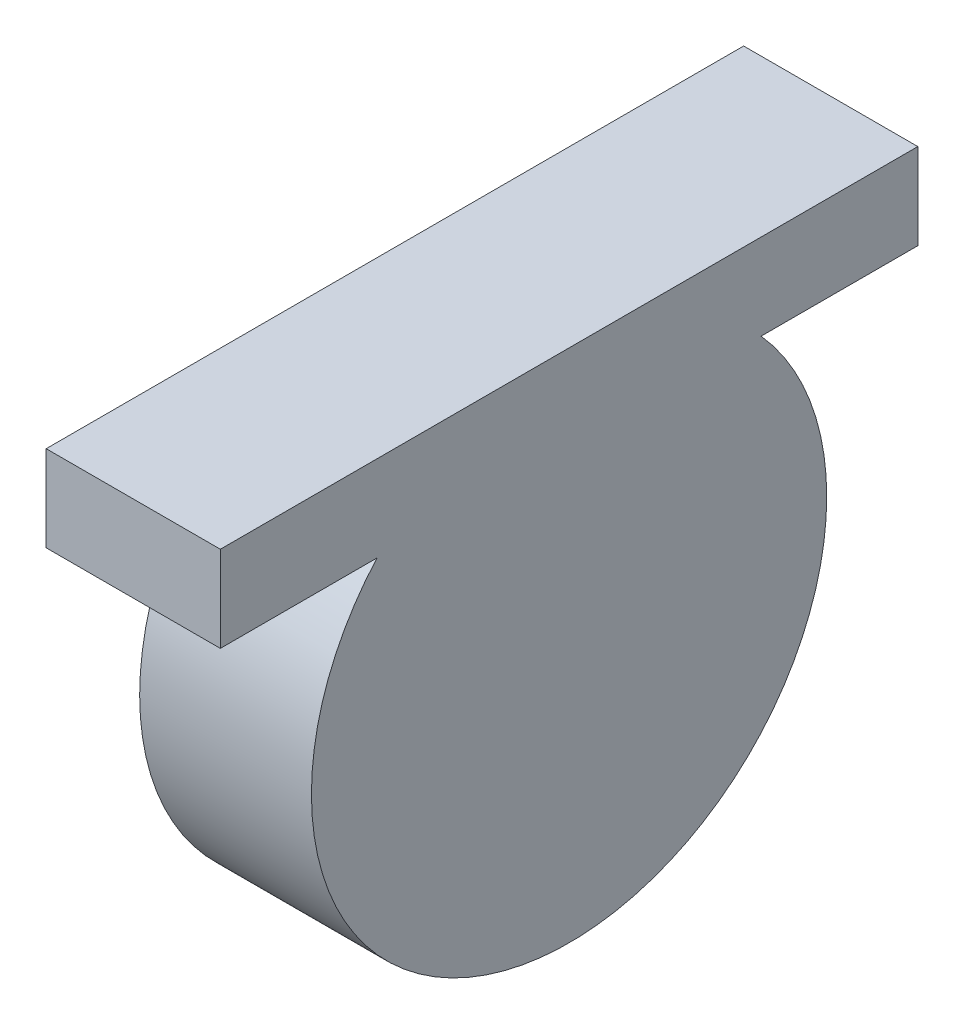
SolidWorks part; units mm, degrees
ref_plane "Front Plane" through (0, 0, 0) normal (0, 0, 1) x (1, 0, 0)
ref_plane "Top Plane" through (0, 0, 0) normal (0, 1, 0) x (1, 0, 0)
ref_plane "Right Plane" through (0, 0, 0) normal (1, 0, 0) x (0, 0, -1)
sketch "Sketch3" plane through (0, 717.6366, 0) normal (0, -1, 0) x (-1, 0, 0)
  line L0 (-524.1514, -762.9166) -> (-524.1514, -558.1792) construction
  line L1 (-524.1514, -712.1166) -> (-498.3984, -712.1166)
  line L2 (-524.1514, -712.1166) -> (-524.1514, -608.9792)
  line L3 (-524.1514, -608.9792) -> (-498.3984, -608.9792)
  line L4 (-498.3984, -712.1166) -> (-498.3984, -608.9792)
  line L5 (-498.3984, -762.9166) -> (-498.3984, -558.1792) construction
  line L6 (-524.1514, -762.9166) -> (-498.3984, -762.9166) construction
  line L7 (-524.1514, -558.1792) -> (-498.3984, -558.1792) construction
  dimension "D1" = 50.8
  dimension "D2" = 50.8
extrude "Boss-Extrude1" add sketch "Sketch3" along normal blind 12.7
sketch "Sketch4" plane through (524.1514, 0, 0) normal (1, 0, 0) x (0, 0, -1)
  line L0 (-660.5479, 717.6366) -> (-660.5479, 679.5366) construction
  line L1 (-608.9792, 717.6366) -> (-712.1166, 717.6366) construction
  circle A0 centre (-660.5479, 679.5366) radius 38.1
  dimension "D1" = 38.1
extrude "Boss-Extrude2" add sketch "Sketch4" against normal blind 25.4
ref_plane "Plane1" through (0, 0, 660.5479) normal (0, 0, 1) x (1, 0, 0)
sketch "Sketch5" plane through (0, 0, 660.5479) normal (0, 0, 1) x (1, 0, 0)
  line L0 (472.4505, 692.7093) -> (547.7665, 668.1914)
  point P2 (473.1607, 701.7644)
  point P3 (546.8438, 645.126)
  point P4 (472.4505, 692.7093)
  point P5 (547.7665, 668.1914)
